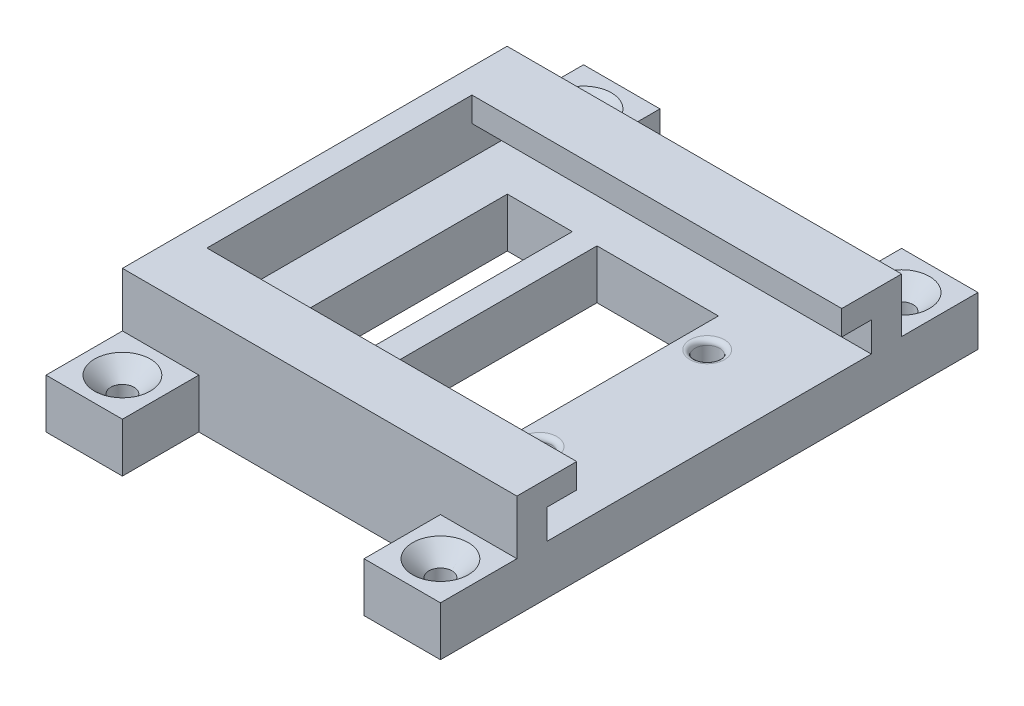
SolidWorks part; units mm, degrees
ref_plane "Front Plane" through (0, 0, 0) normal (0, 0, 1) x (1, 0, 0)
ref_plane "Top Plane" through (0, 0, 0) normal (0, 1, 0) x (1, 0, 0)
ref_plane "Right Plane" through (0, 0, 0) normal (1, 0, 0) x (0, 0, -1)
sketch "Sketch1" plane through (0, 0, 0) normal (1, 0, 0) x (0, 0, -1)
  line L0 (0, 0) -> (65.75, 0) construction
  line L1 (0, 0) -> (65.75, 0)
  line L2 (65.75, 0) -> (65.75, 6)
  line L3 (0, 0) -> (0, 4.9411)
  line L4 (65.75, 6) -> (59.75, 6)
  line L5 (32.875, 0) -> (32.875, 22.5577) construction
  line L6 (0, 6) -> (6, 6)
  line L7 (0, 0) -> (0, 6)
  line L8 (59.75, 6) -> (59.75, 11)
  line L9 (59.75, 11) -> (69.3824, 11)
  line L10 (69.3824, 11) -> (71.8824, 11)
  line L11 (71.8824, 11) -> (71.8824, -5.4629)
  line L12 (71.8824, -5.4629) -> (71.8824, -10)
  line L13 (71.8824, -10) -> (-6.1324, -10)
  line L14 (6, 11) -> (-3.6324, 11)
  line L15 (-6.1324, -5.4629) -> (-6.1324, -10)
  line L16 (-6.1324, 11) -> (-6.1324, -5.4629)
  line L17 (-3.6324, 11) -> (-6.1324, 11)
  line L18 (6, 6) -> (6, 11)
  line L19 (0, 6) -> (6, 6)
  line L20 (0, 0) -> (0, 6)
  line L21 (0, 6) -> (0, 0)
  line L22 (65.75, 0) -> (65.75, 6)
  line L23 (59.75, 6) -> (59.75, 11)
  line L24 (71.8824, 11) -> (71.8824, -10)
  line L25 (-6.1324, -10) -> (-6.1324, 11)
  line L26 (6, 11) -> (6, 6)
  line L27 (0, 6) -> (0, 0)
  point P19 (32.875, -10)
  dimension "D1" = 65.75
  dimension "D2" = 6
  dimension "D3" = 6
  dimension "D4" = 5
  dimension "D5" = 2.5
  dimension "D6" = 10
extrude "Boss-Extrude1" add sketch "Sketch1" along normal blind 75 contours L6 L18 L14 L17 L16 L15 L13 L12 L11 L10 L9 L8 L4 L2 L1 L3 L7 region at (0, -2.7165, -32.875)
sketch "Sketch2" plane through (0, 0, 0) normal (-1, 0, 0) x (0, 0, 1)
  line L1 (-71.8824, 11) -> (6.1324, 11)
  line L2 (-71.8824, 11) -> (-71.8824, -10)
  line L3 (-71.8824, -10) -> (6.1324, -10)
  line L4 (6.1324, 11) -> (6.1324, -10)
extrude "Boss-Extrude2" add sketch "Sketch2" along normal blind 5
sketch "Sketch3" plane through (0, 0, 0) normal (0, 1, 0) x (1, 0, 0)
  line L0 (0, 32.875) -> (75, 32.875) construction
  line L1 (0, 0) -> (0, 65.75) construction
  line L2 (75, 0) -> (75, 65.75) construction
  circle A0 centre (57.59, 15.875) radius 2.5
  circle A1 centre (57.59, 49.875) radius 2.5
  dimension "D3" = 5
  dimension "D1" = 34
sketch "Sketch9" plane through (0, 0, 6.1324) normal (0, 0, 1) x (1, 0, 0)
  line L0 (-5, -10) -> (-5, 0) construction
  line L1 (-5, -10) -> (-5, 11) construction
  line L2 (-5, 0) -> (10.5, 0) construction
  line L3 (-5, -10) -> (-5, 0)
  line L4 (-5, 0) -> (10.5, 0)
  line L5 (10.5, 0) -> (10.5, -10)
  line L6 (75, -10) -> (-5, -10) construction
  line L7 (35, 11) -> (35, -10) construction
  line L8 (75, 11) -> (-5, 11) construction
  line L9 (10.5, -10) -> (-5, -10)
  line L10 (59.5, 0) -> (59.5, -10)
  line L11 (75, 0) -> (59.5, 0)
  line L12 (75, -10) -> (75, 0)
  line L13 (59.5, -10) -> (75, -10)
  dimension "D1" = 10
  dimension "D2" = 15.5
extrude "Boss-Extrude3" add sketch "Sketch9" along normal blind 15.5
sketch "Sketch10" plane through (0, 0, -71.8824) normal (0, 0, -1) x (-1, 0, 0)
  line L0 (-75, -10) -> (-75, 0)
  line L1 (-75, 11) -> (-75, -10) construction
  line L2 (-75, 0) -> (-59.5, 0)
  line L3 (-59.5, 0) -> (-59.5, -10)
  line L4 (-59.5, -10) -> (-75, -10)
  line L5 (-35, 11) -> (-35, -10) construction
  line L6 (-75, 11) -> (5, 11) construction
  line L7 (-75, -10) -> (5, -10) construction
  line L8 (-10.5, 0) -> (-10.5, -10)
  line L9 (5, 0) -> (-10.5, 0)
  line L10 (5, -10) -> (5, 0)
  line L11 (-10.5, -10) -> (5, -10)
  dimension "D1" = 10
  dimension "D2" = 15.5
extrude "Boss-Extrude4" add sketch "Sketch10" along normal blind 15.5
sketch "Sketch11" plane through (0, 0, 0) normal (0, 1, 0) x (1, 0, 0)
  line L0 (35, -6.1324) -> (35, -11.9237) construction
  line L1 (75, -6.1324) -> (-5, -6.1324) construction
  line L2 (2.75, -13.8824) -> (6.9, -13.8824) construction
  line L3 (75, 32.875) -> (90.9739, 32.875) construction
  line L4 (75, 0) -> (75, 65.75) construction
  circle A0 centre (2.75, -13.8824) radius 2.35
  circle A1 centre (67.25, -13.8824) radius 2.35
  circle A2 centre (67.25, 79.6324) radius 2.35
  circle A3 centre (2.75, 79.6324) radius 2.35
  dimension "D1" = 4.7
  dimension "D2" = 4.15
extrude "Cut-Extrude6" cut sketch "Sketch11" against normal through all both and the other way through all
fillet "Fillet2" radius 3.3 1 edges at (2.75, 0, 11.5324) conic radius 140
fillet "Fillet3" radius 3.3 3 edges at (67.25, 0, 11.5324) (67.25, 0, -81.9824) (2.75, 0, -81.9824) conic radius 140
sketch "Sketch12" plane through (0, 0, 0) normal (0, 1, 0) x (1, 0, 0)
  line L0 (0, 32.875) -> (75, 32.875) construction
  line L1 (0, 0) -> (0, 65.75) construction
  line L2 (75, 0) -> (75, 65.75) construction
extrude "Cut-Extrude1" cut sketch "Sketch3" against normal through all both and the other way through all
fillet "Fillet1" radius 1 2 edges at (57.59, 0, -47.375) (57.59, 0, -13.375)
sketch "Sketch7" plane through (0, 0, 0) normal (0, 1, 0) x (1, 0, 0)
  line L0 (45.1719, 56.936) -> (28.1719, 56.936)
  line L1 (0, 32.875) -> (9.993, 33.2501) construction
  line L3 (0, 0) -> (0, 65.75) construction
  line L4 (28.1719, 56.936) -> (28.1719, 9.564)
  line L6 (52.7957, 56.936) -> (45.1719, 56.936)
  line L7 (52.7957, 56.936) -> (52.7957, 9.564)
  line L10 (52.7957, 9.564) -> (28.1719, 9.564)
  line L11 (28.1719, 33.25) -> (23.1719, 33.25) construction
  line L13 (9.993, 33.2501) -> (9.993, 9.564)
  line L14 (9.993, 9.564) -> (23.1719, 9.564)
  line L15 (23.1719, 33.25) -> (23.1719, 9.564)
  line L17 (23.1719, 33.25) -> (23.1719, 56.936)
  line L18 (23.1719, 56.936) -> (9.993, 56.936)
  line L19 (9.993, 33.2501) -> (9.993, 56.936)
  dimension "D1" = 17
  dimension "D2" = 10
  dimension "D3" = 5
extrude "Cut-Extrude5" cut sketch "Sketch7" against normal blind 25
